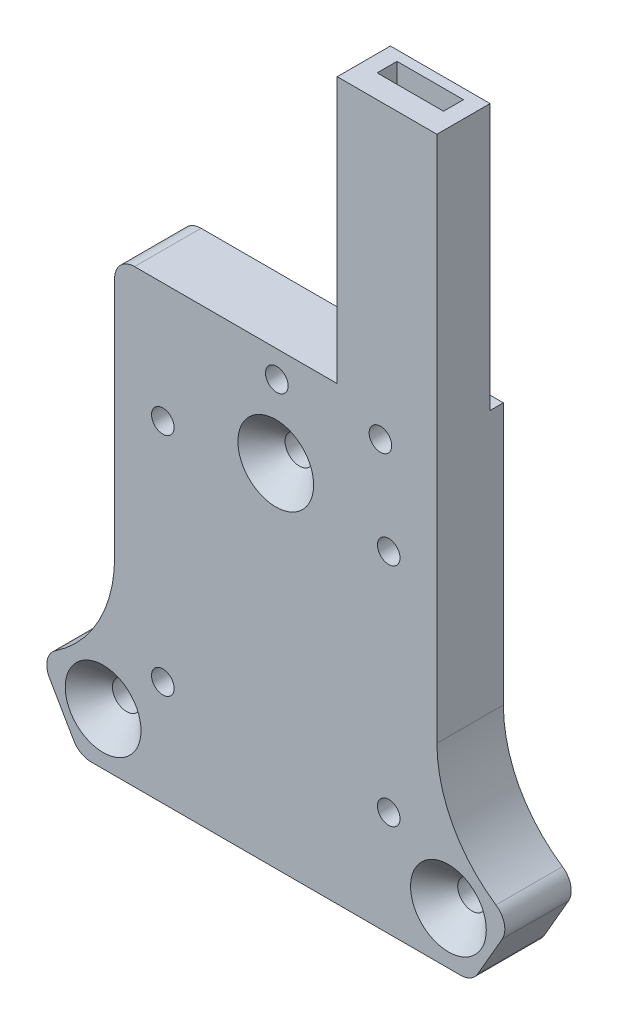
SolidWorks part; units mm, degrees
note: '?' marks a value the reader was unsure of.
other "tool plate"
material "PET"
ref_plane "Front" through (0, 0, 0) normal (0, 0, 1) x (1, 0, 0)
ref_plane "Top" through (0, 0, 0) normal (0, 1, 0) x (1, 0, 0)
ref_plane "Right" through (0, 0, 0) normal (1, 0, 0) x (0, 0, -1)
sketch "Sketch1" plane through (0, 0, 0) normal (0, 0, 1) x (1, 0, 0)
  line L0 (0, 0) -> (0, 30) construction
  line L1 (0, 0) -> (-25.9808, -15) construction
  line L2 (0, 0) -> (25.9808, -15) construction
  line L4 (-6, -1) -> (6, -1)
  line L5 (-6, -1) -> (-6, 1)
  line L6 (-6, 1) -> (6, 1)
  line L7 (6, -1) -> (6, 1)
  line L8 (-6, -1) -> (6, 1) construction
  line L9 (-6, 1) -> (6, -1) construction
  circle A0 centre (0, 0) radius 2.5
  circle A1 centre (0, 30) radius 4
  circle A2 centre (25.9808, -15) radius 4
  circle A3 centre (-25.9808, -15) radius 4
  dimension "D4" = 5
  dimension "D7" = 8
  dimension "D1" = 30
  dimension "D2" = 120
  dimension "D3" = 120
  dimension "D5" = 12
  dimension "D6" = 2
ref_plane "Plane1" through (0, 30, 0) normal (0, 1, 0) x (1, 0, 0)
sketch "Sketch10" plane through (0, 30, 0) normal (0, 1, 0) x (1, 0, 0)
  line L0 (0, 7.5) -> (0, 0) construction
  line L1 (-6, 0) -> (6, 0) construction
  circle A0 centre (0, 3.5) radius 4
  dimension "D1" = 8
  dimension "D2" = 7.5
sketch "Sketch2" plane through (0, 0, 0) normal (0, 0, 1) x (1, 0, 0)
  line L0 (0, 0) -> (0, 30) construction
  line L1 (0, 0) -> (0, 30) construction
  line L2 (-24.25, 45) -> (24.25, 45)
  line L3 (24.25, 45) -> (24.25, -5.9178)
  line L4 (-24.25, 45) -> (-24.25, -5.9178)
  line L5 (24.25, -5.9178) -> (35.5429, -12.4378)
  line L6 (35.5429, -12.4378) -> (29.5429, -22.8301)
  line L7 (29.5429, -22.8301) -> (-29.5429, -22.8301)
  line L8 (0, 0) -> (25.9808, -15) construction
  line L9 (32.0429, -18.5) -> (25.9808, -15) construction
  line L10 (-35.5429, -12.4378) -> (-29.5429, -22.8301)
  line L11 (-24.25, -5.9178) -> (-35.5429, -12.4378)
  circle A0 centre (25.9808, -15) radius 4 construction
  circle A1 centre (0, 0) radius 7.5
  point P8 (0, 45)
  point P19 (0, -22.8301)
  dimension "D3" = 7
  dimension "D5" = 15
  dimension "D1" = 24.25
  dimension "D2" = 15
  dimension "D4" = 12
  dimension "D6" = 5
extrude "Boss-Extrude1" add sketch "Sketch2" along normal blind 10
hole_wizard "CSK for M4 Flat Head Machine Screw1" positions "Sketch8" profile "Sketch9" countersink size "M4" standard "ANSI Metric"
sketch "Sketch8" plane through (0, 0, 10) normal (0, 0, 1) x (1, 0, 0)
  point P0 (-25.9808, -15)
  point P3 (0, 30)
  point P6 (25.9808, -15)
sketch "Sketch9" plane through (-25.9808, -15, 10) normal (1, 0, 0) x (0, -1, 0)
  line L0 (0, 0) -> (0, 11.2909)
  line L1 (0, 11.2909) -> (2.15, 9.999)
  line L2 (2.15, 9.999) -> (2.15, 3.55)
  line L3 (2.15, 3.55) -> (5.7, 0)
  line L5 (5.7, 0) -> (0, 0)
  line L6 (-2.15, 3.55) -> (-5.7, 0) construction
  line L10 (0, 11.2909) -> (-2.15, 9.999) construction
  line L11 (0, -6.35) -> (0, 107.95) construction
  dimension "Hole Dia." = 4.3
  dimension "Hole Depth" = 9.999
  dimension "Near C'Sink Dia." = 11.4
  dimension "Near C'Sink Angle" = 90
  dimension "Drill Angle" = 118
fillet "Fillet1" radius 20 2 edges at (-24.25, -5.9178, 5) (24.25, -5.9178, 5)
ref_axis "Axis2" through (0, 30, 0) along (0, 0, 1)?
ref_plane "Plane5" through (0, 30, 0) normal (0, 1, 0) x (1, 0, 0)
sketch "Sketch46" plane through (0, 30, 0) normal (0, 1, 0) x (1, 0, 0)
  line L0 (0, 0) -> (0, 0.3) construction
  line L1 (0, 5.3) -> (0, -4.7)
  line L2 (0, 7.5) -> (0, 0) construction
  circle A0 centre (0, 0.3) radius 5 construction
  arc A1 (0, -4.7) -> (0, 5.3) centre (0, 0.3) cw
  dimension "D1" = 10
  dimension "D2" = 3.2
revolve "tool ball cutout" cut sketch "Sketch46" angle 360 about L0
pattern_circular "CirPattern2" count 3 over 360 about axis through (0, 0, 0) along (0, 0, 1) of "tool ball cutout"
fillet "Fillet2" radius 3 6 edges at (24.25, 45, 5) (-24.25, 45, 5) (-29.5429, -22.8301, 5) (-35.5429, -12.4378, 5) (29.5429, -22.8301, 5) (35.5429, -12.4378, 5)
sketch "Sketch47" plane through (0, 0, 0) normal (0, 0, -1) x (-1, 0, 0)
  line L0 (0, 0) -> (0, 42.2664) construction
  line L1 (-17, 42.2664) -> (-17, -19.1503) construction
  line L2 (17, 36.2499) -> (17, -22.2786) construction
  line L3 (-17, 27) -> (17, 27) construction
  line L4 (-17, -7) -> (17, -7) construction
  line L5 (-21.25, 45) -> (21.25, 45) construction
  circle A0 centre (-17, 27) radius 1.7
  circle A1 centre (17, 27) radius 1.7
  circle A2 centre (17, -7) radius 1.7
  circle A3 centre (-17, -7) radius 1.7
  dimension "D5" = 3.4
  dimension "D6" = 3.4
  dimension "D7" = 3.4
  dimension "D8" = 3.4
  dimension "D1" = 34
  dimension "D2" = 17
  dimension "D3" = 34
  dimension "D4" = 18
extrude "Cut-Extrude1" cut sketch "Sketch47" against normal through all
sketch "Sketch49" plane through (0, 45, 0) normal (0, 1, 0) x (1, 0, 0)
  line L0 (21.25, 0) -> (-21.25, 0) construction
  line L1 (9.25, -10) -> (24.25, -10)
  line L2 (9.25, -10) -> (9.25, 0)
  line L3 (9.25, 0) -> (24.25, 0)
  line L4 (24.25, -10) -> (24.25, 0)
  line L5 (24.25, 0) -> (24.25, -10) construction
  line L6 (11.75, -3.5) -> (21.75, -3.5)
  line L7 (11.75, -3.5) -> (11.75, -6.5)
  line L8 (11.75, -6.5) -> (21.75, -6.5)
  line L9 (21.75, -3.5) -> (21.75, -6.5)
  dimension "D1" = 15
  dimension "D2" = 2.5
  dimension "D3" = 10
  dimension "D4" = 3
  dimension "D5" = 3.5
extrude "Boss-Extrude2" add sketch "Sketch49" along normal blind 40
chamfer "Chamfer1" distance 2 angle 45 4 edges at (15.3, -7, 0) (-18.7, -7, 0) (-18.7, 27, 0) (15.3, 27, 0)
sketch "Sketch51" plane through (0, 45, 0) normal (0, -1, 0) x (1, 0, 0)
  line L1 (24.25, 10) -> (21.25, 10)
  line L2 (24.25, 10) -> (24.25, 0)
  line L3 (24.25, 0) -> (21.25, 0)
  line L4 (21.25, 10) -> (21.25, 0)
extrude "Boss-Extrude3" add sketch "Sketch51" along normal up to next
sketch "Sketch52" plane through (0, 0, 10) normal (0, 0, 1) x (1, 0, 0)
  line L0 (24.25, 45) -> (31.75, 45)
  line L1 (24.25, 5.6292) -> (24.25, 85) construction
  line L2 (31.75, 45) -> (31.75, -9.9833)
  line L3 (24.25, 45) -> (24.25, 5.6292)
  arc A0 (24.25, 5.6292) -> (33.1366, -10.9989) centre (44.25, 5.6292) ccw construction
  arc A1 (24.25, 5.6292) -> (31.75, -9.9833) centre (44.25, 5.6292) ccw
  dimension "D1" = 7.5
extrude "Boss-Extrude4" add sketch "Sketch52" against normal up to surface (10 mm away) up to face at (-0.2248, 11.4014, 0)
sketch "Sketch48" plane through (0, 0, 10) normal (0, 0, 1) x (1, 0, 0)
  line L0 (9.25, 45) -> (-21.25, 45) construction
  line L2 (15.7503, 41) -> (0.1503, 41) construction
  line L3 (-24.25, 42) -> (-24.25, 5.6292) construction
  circle A0 centre (0.1503, 41) radius 1.7
  circle A1 centre (15.7503, 41) radius 1.7
  dimension "D1" = 3.4
  dimension "D2" = 3.4
  dimension "D3" = 15.6
  dimension "D4" = 4
  dimension "D5" = 24.4003
extrude "Cut-Extrude2" cut sketch "Sketch48" against normal through all
chamfer "Chamfer4" distance 2 angle 45 2 edges at (1.8503, 41, 0) (17.4503, 41, 0)
chamfer "Chamfer3" distance 2 angle 45 3 edges at (9.25, 65, 0) (16.75, 85, 0) (24.25, 65, 0)
sketch "Sketch53" plane through (0, 0, 0) normal (0, 0, -1) x (-1, 0, 0)
  circle A0 centre (0, 0) radius 15.5
  dimension "D1" = 31
extrude "Cut-Extrude3" cut sketch "Sketch53" against normal blind 1.5
sketch "Sketch54" plane through (0, 0, 1.5) normal (0, 0, -1) x (-1, 0, 0)
  circle A0 centre (0, 0) radius 7.5
extrude "Boss-Extrude5" add sketch "Sketch54" against normal up to surface (8.5 mm away) up to face at (1.8503, 41, 10)
sketch "Sketch55" plane through (0, 0, 0) normal (0, 0, -1) x (-1, 0, 0)
  line L0 (-24.25, 45) -> (-24.25, 5.6292)
  line L2 (-31.75, -9.9833) -> (-31.75, 45)
  line L3 (-31.75, 45) -> (-24.25, 45)
  arc A2 (-31.75, -9.9833) -> (-24.25, 5.6292) centre (-44.25, 5.6292) ccw
  arc A3 (-33.1366, -10.9989) -> (-31.75, -9.9833) centre (-44.25, 5.6292) ccw construction
extrude "Cut-Extrude4" cut sketch "Sketch55" against normal through all
